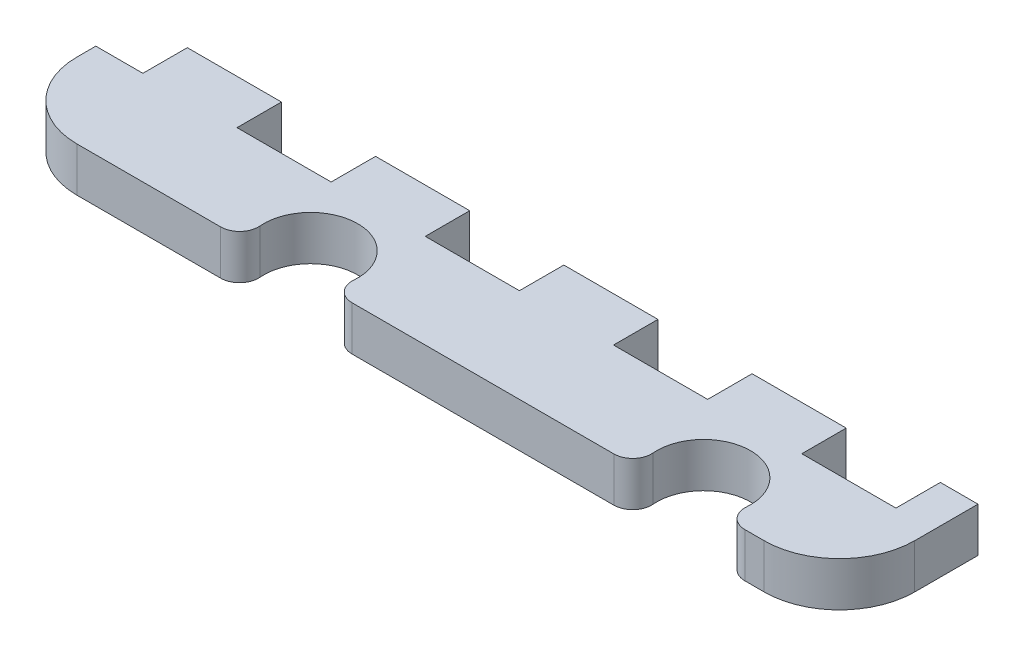
SolidWorks part; units mm, degrees
ref_plane "Front Plane" through (0, 0, 0) normal (0, 0, 1) x (1, 0, 0)
ref_plane "Top Plane" through (0, 0, 0) normal (0, 1, 0) x (1, 0, 0)
ref_plane "Right Plane" through (0, 0, 0) normal (1, 0, 0) x (0, 0, -1)
sketch "Sketch1" plane through (0, 0, 0) normal (0, 1, 0) x (1, 0, 0)
  line L0 (0, 0) -> (12.7, 0)
  line L1 (12.7, 0) -> (12.7, -5.9944)
  line L2 (12.7, -5.9944) -> (25.4, -5.9944)
  line L3 (0, 0) -> (0, -5.9944)
  line L4 (25.4, 0) -> (38.1, 0)
  line L5 (38.1, 0) -> (38.1, -5.9944)
  line L6 (38.1, -5.9944) -> (50.8, -5.9944)
  line L7 (25.4, 0) -> (25.4, -5.9944)
  line L8 (50.8, 0) -> (63.5, 0)
  line L9 (63.5, 0) -> (63.5, -5.9944)
  line L10 (63.5, -5.9944) -> (76.2, -5.9944)
  line L11 (50.8, 0) -> (50.8, -5.9944)
  line L12 (76.2, 0) -> (88.9, 0)
  line L13 (88.9, 0) -> (88.9, -5.9944)
  line L14 (88.9, -5.9944) -> (101.6, -5.9944)
  line L15 (76.2, 0) -> (76.2, -5.9944)
  line L16 (101.6, 0) -> (106.68, 0)
  line L17 (106.68, 0) -> (106.68, -5.9944)
  line L18 (0, -5.9944) -> (-6.35, -5.9944)
  line L19 (101.6, 0) -> (101.6, -5.9944)
  line L20 (114.3, -5.9944) -> (127, -5.9944) [skipped]
  line L21 (101.6, 0) -> (114.3, 0) [skipped]
  line L22 (114.3, 0) -> (114.3, -5.9944) [skipped]
  line L23 (-6.35, -5.9944) -> (-6.35, -8.5344)
  line L24 (3.81, -18.6944) -> (23.2021, -18.6944)
  line L25 (106.68, -8.5344) -> (106.68, -5.9944)
  line L26 (40.9209, -18.6944) -> (76.2444, -18.6944)
  line L27 (93.9169, -18.6944) -> (96.52, -18.6944)
  arc A0 (96.52, -18.6944) -> (106.68, -8.5344) centre (96.52, -8.5344) ccw
  arc A1 (-6.35, -8.5344) -> (3.81, -18.6944) centre (3.81, -8.5344) ccw
  arc A2 (38.3896, -15.9438) -> (25.7334, -15.9438) centre (32.0615, -15.4174) ccw
  arc A3 (25.7334, -15.9438) -> (23.2021, -18.6944) centre (23.2021, -16.1544) cw
  arc A4 (38.3896, -15.9438) -> (40.9209, -18.6944) centre (40.9209, -16.1544) ccw
  arc A5 (91.3857, -15.9433) -> (78.7757, -15.9433) centre (85.0807, -15.4174) ccw
  arc A6 (76.2444, -18.6944) -> (78.7757, -15.9433) centre (76.2444, -16.1544) ccw
  arc A7 (93.9169, -18.6944) -> (91.3857, -15.9433) centre (93.9169, -16.1544) cw
  point P42 (37.5006, -18.6944)
  dimension "D2" = 10.16
  dimension "D3" = 10.16
  dimension "D4" = 2.54
  dimension "D5" = 2.54
  dimension "D6" = 2.54
  dimension "D7" = 2.54
  dimension "D1" = 5
extrude "Boss-Extrude1" add sketch "Sketch1" along normal blind 5.9944
